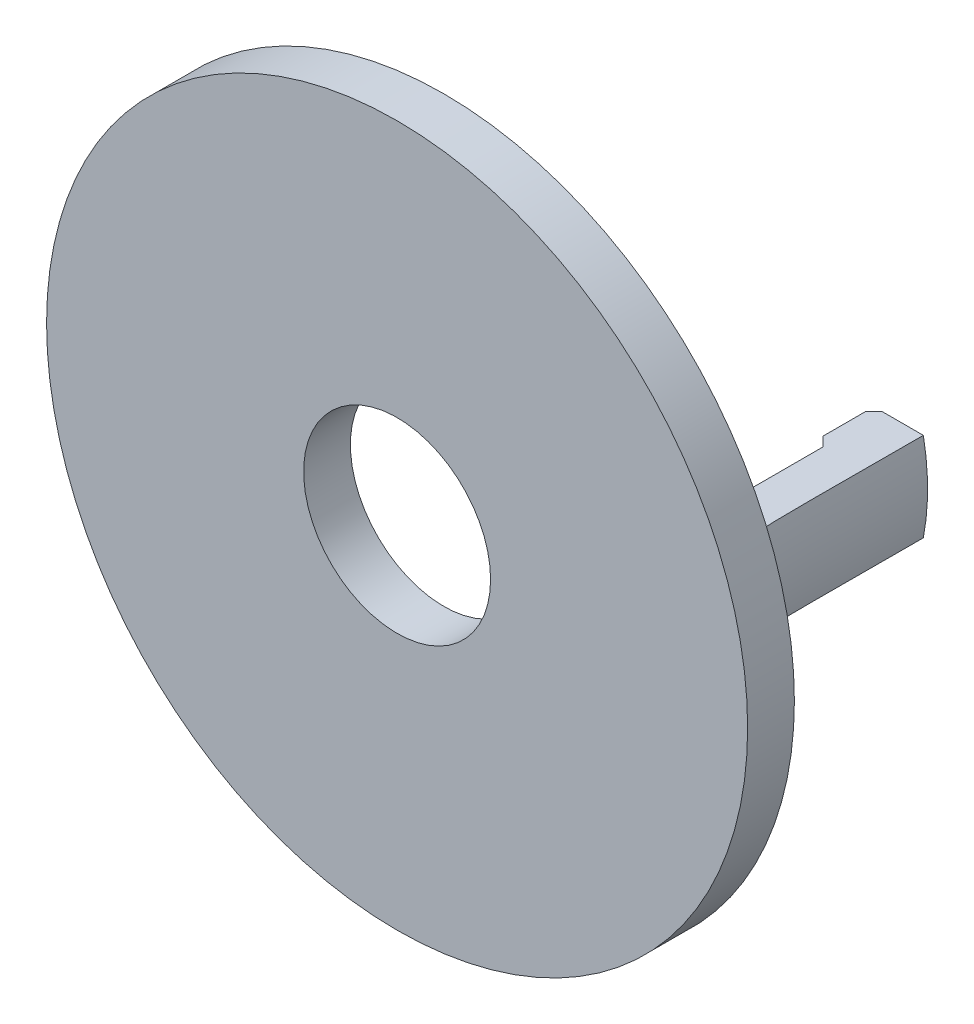
SolidWorks part; units mm, degrees
ref_plane "Front" through (0, 0, 0) normal (0, 0, 1) x (1, 0, 0)
ref_plane "Top" through (0, 0, 0) normal (0, 1, 0) x (1, 0, 0)
ref_plane "Right" through (0, 0, 0) normal (1, 0, 0) x (0, 0, -1)
sketch "Sketch1" plane through (0, 0, 0) normal (0, 0, 1) x (1, 0, 0)
  circle A0 centre (0, 0) radius 26.5
  circle A1 centre (0, 0) radius 37.5
  circle A2 centre (-2, 0) radius 26.5
  dimension "D1" = 53
  dimension "D2" = 75
  dimension "D3" = 2
sketch "Sketch4" plane through (0, 0, 0) normal (0, 0, 1) x (1, 0, 0)
  circle A0 centre (0, 0) radius 37.5
  dimension "D1" = 75
extrude "Boss-Extrude2" add sketch "Sketch4" along normal blind 5
sketch "Sketch5" plane through (0, 0, 5) normal (0, 0, 1) x (1, 0, 0)
  circle A0 centre (0, 0) radius 10
  dimension "D1" = 20
extrude "Cut-Extrude1" cut sketch "Sketch5" against normal through all
sketch "Sketch6" plane through (0, 0, 0) normal (0, 1, 0) x (1, 0, 0)
  line L0 (20, 0) -> (26.5, 0) construction
  line L1 (26.5, 0) -> (26.5, 27) construction
  line L2 (17.3536, 0) -> (26.5, 0)
  line L3 (26.5, 27) -> (20, 27) construction
  line L4 (20, 27) -> (18.5, 25.5) construction
  line L5 (18.5, 21) -> (20, 19.5) construction
  line L6 (20, 19.5) -> (20, 0) construction
  line L7 (20.25, 20.3107) -> (20.25, 2.8964)
  line L8 (20, 3) -> (17, 0) construction
  line L9 (20.25, 20.3107) -> (19.25, 21.3107)
  line L10 (18.5, 25.5) -> (18.5, 21) construction
  line L11 (19.25, 21.3107) -> (19.25, 25.8964)
  line L12 (26.5, 0) -> (26.5, 26.75)
  line L13 (17, 0) -> (20, 0) construction
  line L14 (20.25, 2.8964) -> (17.3536, 0)
  line L15 (19.25, 25.8964) -> (20.1036, 26.75)
  line L16 (20.1036, 26.75) -> (26.5, 26.75)
  line L17 (25, 26.5113) -> (25, 41.0721) construction
  line L18 (25, 12.4795) -> (25, 18.7128) construction
  spline S0 degree 3 poles (25, 26.75) (25, 22.7282) (24.9901, 20.5425) (25.0119, 14.9424) (24.7749, 4.9839) (26.5, 0) knots 0 0 0 0 0.446605 0.546605 1 1 1 1
  dimension "D1" = 135
  dimension "D2" = 6.5
  dimension "D3" = 8
  dimension "D4" = 27
  dimension "D5" = 7.5
  dimension "D6" = 0.25
  dimension "D7" = 0.25
  dimension "D8" = 0.25
  dimension "D9" = 0.75
  dimension "D10" = 3
  dimension "D11" = 3
  dimension "D12" = 0.25
  dimension "D13" = 1.5
  dimension "D14" = 0.75
extrude "Boss-Extrude3" add sketch "Sketch6" along normal blind 4.75 and the other way blind 4.75 contours L16 L15 L11 L9 L7 L14 L2 | L12 L16 region at (22.5194, 0, -13.0102) region at (25.7982, 0, -14.9997)
extrude "Cut-Extrude2" cut sketch "Sketch1" against normal through all contours A1 A2 A0 region at (-36.4393, 0, 0)
ref_axis "Axis1" through (0, 0, 0) along (0, 0, -1)
revolve "Cut-Revolve1" cut sketch "Sketch6<4>" angle 360 about axis through (0, 0, 0) along (0, 0, -1) region at (25.7982, 0, -14.9997)
sketch "Sketch6<4>" plane through (0, 0, 0) normal (0, 1, 0) x (1, 0, 0) same geometry as "Sketch6"
mirror "Mirror1" about plane through (0, 0, 0) normal (1, 0, 0) of "Boss-Extrude3", "Cut-Extrude2", "Cut-Revolve1"
equation "\"mate_room\"= 0.25"
equation "\"D6@Sketch6\"=\"mate_room\""
equation "\"D8@Sketch6\"=\"mate_room\""
equation "\"D7@Sketch6\"=\"mate_room\""
equation "\"D9@Sketch6\"=\"removal_room\""
equation "\"D12@Sketch6\"=\"mate_room\""
equation "\"D14@Sketch6\"=\"removal_room\""
equation "\"removal_room\"= 0.75"
equation "\"large_inner_axle_diameter\"=20"
equation "\"D1@Sketch5\"=\"large_inner_axle_diameter\""
